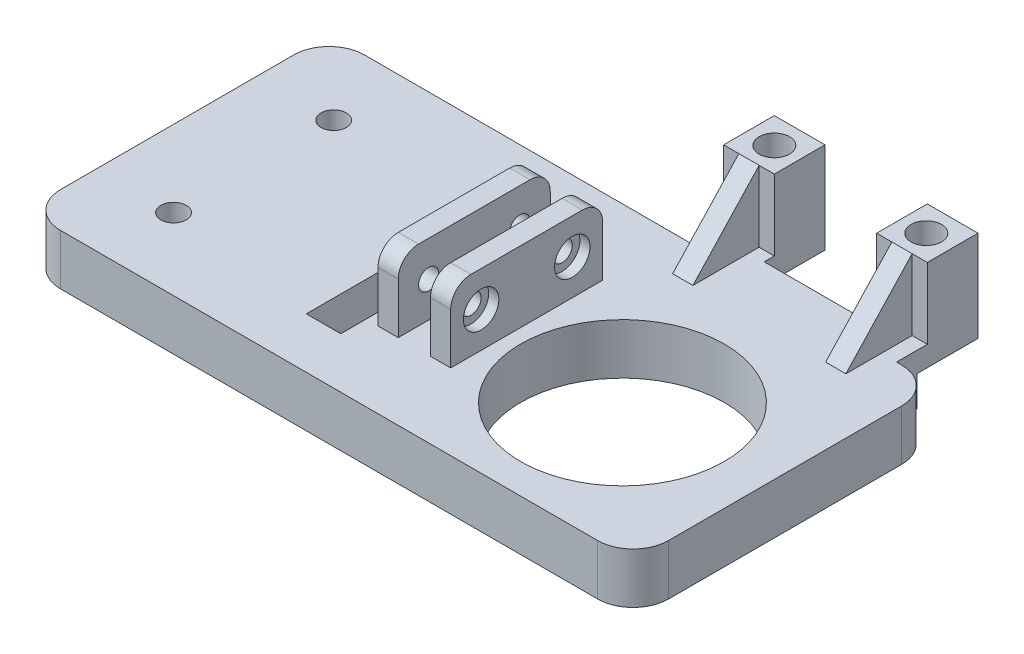
SolidWorks part; units mm, degrees
ref_plane "Front Plane" through (0, 0, 0) normal (0, 0, 1) x (1, 0, 0)
ref_plane "Top Plane" through (0, 0, 0) normal (0, 1, 0) x (1, 0, 0)
ref_plane "Right Plane" through (0, 0, 0) normal (1, 0, 0) x (0, 0, -1)
sketch "Sketch1" plane through (0, 0, 0) normal (0, 1, 0) x (1, 0, 0)
  line L1 (-30, 15) -> (30, 15)
  line L2 (-30, 15) -> (-30, -15)
  line L3 (-30, -15) -> (30, -15)
  line L4 (30, 15) -> (30, -15)
  line L5 (-30, 15) -> (30, -15) construction
  line L6 (-30, -15) -> (30, 15) construction
  point P0 (0, 0)
  dimension "D1" = 60
  dimension "D2" = 30
extrude "Boss-Extrude1" add sketch "Sketch1" along normal blind 5
sketch "Sketch2" plane through (0, 5, 0) normal (0, 1, 0) x (1, 0, 0)
  line L0 (-30, 15) -> (-30, -15) construction
  line L1 (-7.25, -10) -> (-3.85, -10)
  line L2 (-7.25, -10) -> (-7.25, 10)
  line L3 (-7.25, 10) -> (-3.85, 10)
  line L4 (-3.85, -10) -> (-3.85, 10)
  line L5 (-22.45, 7.9) -> (-22.45, -7.9) construction
  circle A0 centre (-22.45, -7.9) radius 1.25
  circle A1 centre (-22.45, 7.9) radius 1.25
  point P8 (-22.45, 0)
  point P9 (-7.25, 0)
  point P10 (-30, 0)
  dimension "D2" = 2.5
  dimension "D1" = 15.8
  dimension "D3" = 3.4
  dimension "D4" = 22.75
  dimension "D5" = 15.2
  dimension "D6" = 20
extrude "Cut-Extrude1" cut sketch "Sketch2" against normal through all
sketch "Sketch3" plane through (0, 0, 0) normal (0, -1, 0) x (1, 0, 0)
  line L0 (30, 15) -> (30, -15) construction
  line L1 (-30, 15) -> (30, 15) construction
  circle A0 centre (15.95, 2) radius 10.05
  dimension "D1" = 20.1
  dimension "D2" = 14.05
  dimension "D3" = 13
extrude "Cut-Extrude2" cut sketch "Sketch3" against normal through all
sketch "Sketch4" plane through (0, 0, -15) normal (0, 0, -1) x (-1, 0, 0)
  line L0 (-30, 5) -> (30, 5) construction
  line L1 (-26, 5) -> (-5.9, 5)
  line L2 (-26, 5) -> (-26, 0)
  line L3 (-26, 0) -> (-5.9, 0)
  line L4 (-5.9, 5) -> (-5.9, 0)
  line L5 (-30, 0) -> (30, 0) construction
  line L6 (-30, 5) -> (-30, 0) construction
  dimension "D1" = 4
  dimension "D2" = 20.1
extrude "Boss-Extrude2" add sketch "Sketch4" along normal blind 8.04
sketch "Sketch5" plane through (0, 5, 0) normal (0, 1, 0) x (1, 0, 0)
  line L1 (26, 23.04) -> (21, 23.04)
  line L2 (26, 23.04) -> (26, 18.04)
  line L3 (26, 18.04) -> (21, 18.04)
  line L4 (21, 23.04) -> (21, 18.04)
  circle A0 centre (23.45, 20.49) radius 1.5
  dimension "D1" = 3
  dimension "D2" = 5
  dimension "D3" = 2.55
  dimension "D4" = 2.55
  dimension "D5" = 5
extrude "Boss-Extrude3" add sketch "Sketch5" along normal blind 7
ref_plane "Plane1" through (15.95, 0, 0) normal (-1, 0, 0) x (0, 0, 1)
sketch "Sketch6" plane through (0, 0, 0) normal (0, -1, 0) x (1, 0, 0)
  line L0 (26, -23.04) -> (5.9, -23.04) construction
  line L1 (21, -23.04) -> (10.9, -23.04)
  line L2 (21, -23.04) -> (21, -17.04)
  line L3 (21, -17.04) -> (10.9, -17.04)
  line L4 (10.9, -23.04) -> (10.9, -17.04)
  line L5 (26, -23.04) -> (26, -15) construction
  line L6 (5.9, -23.04) -> (5.9, -15) construction
  circle A0 centre (23.45, -20.49) radius 1.5
  circle A1 centre (8.45, -20.49) radius 1.5
  point P11 (15.95, -23.04)
  point P12 (15.95, -17.04)
  dimension "D1" = 3
  dimension "D2" = 6
  dimension "D3" = 10.1
  dimension "D4" = 2.55
  dimension "D5" = 2.55
  dimension "D6" = 2.55
extrude "Cut-Extrude3" cut sketch "Sketch6" against normal blind 5
ref_plane "Plane2" through (23.5, 0, 0) normal (1, 0, 0) x (0, 0, -1)
sketch "Sketch8" plane through (23.5, 0, 0) normal (1, 0, 0) x (0, 0, -1)
  line L0 (18.04, 12) -> (11.5, 5)
  line L1 (18.04, 12) -> (18.04, 5) construction
  line L2 (-15, 5) -> (15, 5) construction
  line L4 (18.04, 5) -> (15, 5) construction
  dimension "D1" = 3.5
  dimension "D2" = 7
rib "Rib7" sketch "Sketch8" sketch "Sketch8" thickness 2 extrusion direction parallel to sketch draft on no parameters "D1"=2
sketch "Sketch9" plane through (0, 0, 0) normal (0, -1, 0) x (1, 0, 0)
  line L0 (26, -23.04) -> (26, -15) construction
  line L1 (26, -17.04) -> (21, -17.04)
  line L2 (26, -17.04) -> (26, -23.04)
  line L3 (26, -23.04) -> (21, -23.04)
  line L4 (21, -17.04) -> (21, -23.04)
extrude "Cut-Extrude4" cut sketch "Sketch9" against normal blind 3
mirror "Mirror1" about plane through (15.95, 0, 0) normal (-1, 0, 0) of "Cut-Extrude4", "Boss-Extrude3", "Rib7"
sketch "Sketch10" plane through (0, 5, 0) normal (0, 1, 0) x (1, 0, 0)
  line L0 (0.9125, -11.5514) -> (0.9125, 11.1943) construction
  line L1 (4.5, -7.5) -> (2.5, -7.5)
  line L2 (4.5, -7.5) -> (4.5, 7.5)
  line L3 (4.5, 7.5) -> (2.5, 7.5)
  line L4 (2.5, -7.5) -> (2.5, 7.5)
  line L5 (-0.675, -7.5) -> (-2.675, -7.5)
  line L6 (-0.675, -7.5) -> (-0.675, 7.5)
  line L7 (-0.675, 7.5) -> (-2.675, 7.5)
  line L8 (-2.675, -7.5) -> (-2.675, 7.5)
  line L10 (30, -15) -> (30, 15) construction
  point P12 (4.5, 0)
  point P13 (30, 0)
  dimension "D1" = 3.175
  dimension "D2" = 2
  dimension "D3" = 15
  dimension "D4" = 25.5
extrude "Boss-Extrude4" add sketch "Sketch10" along normal blind 7
sketch "Sketch11" plane through (4.5, 0, 0) normal (1, 0, 0) x (0, 0, -1)
  line L0 (-7.5, 12) -> (-7.5, 5) construction
  line L1 (7.5, 12) -> (7.5, 5) construction
  circle A0 centre (4.5, 8.5) radius 1.75
  circle A1 centre (-4.5, 8.5) radius 1.75
  point P7 (-7.5, 8.5)
  dimension "D1" = 3.5
  dimension "D2" = 3
  dimension "D3" = 3
extrude "Cut-Extrude5" cut sketch "Sketch11" against normal blind 1
sketch "Sketch12" plane through (3.5, 0, 0) normal (1, 0, 0) x (0, 0, -1)
  circle A0 centre (-4.5, 8.5) radius 1
  circle A1 centre (4.5, 8.5) radius 1
  dimension "D1" = 2
extrude "Cut-Extrude6" cut sketch "Sketch12" against normal blind 11
fillet "Fillet1" radius 3.5 4 edges at (-30, 2.5, 15) (-30, 2.5, -15) (30, 2.5, 15) (30, 2.5, -15)
fillet "Fillet2" radius 2 4 edges at (-1.675, 12, 7.5) (3.5, 12, 7.5) (-1.675, 12, -7.5) (3.5, 12, -7.5)
